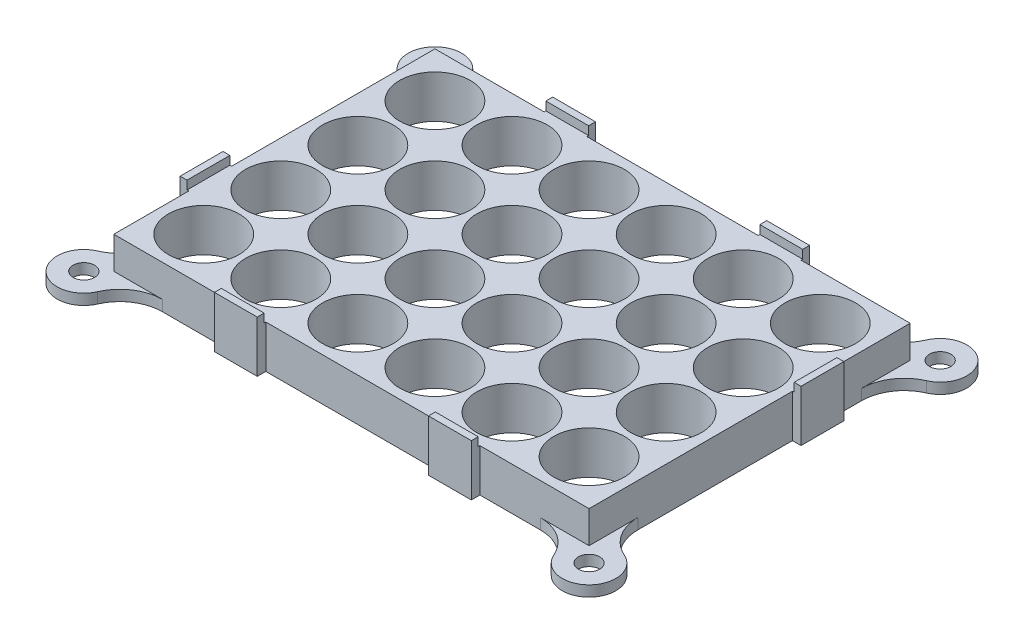
SolidWorks part; units mm, degrees
ref_plane "Front Plane" through (0, 0, 0) normal (0, 0, 1) x (1, 0, 0)
ref_plane "Top Plane" through (0, 0, 0) normal (0, 1, 0) x (1, 0, 0)
ref_plane "Right Plane" through (0, 0, 0) normal (1, 0, 0) x (0, 0, -1)
sketch "Sketch3" plane through (0, 0, 0) normal (0, 1, 0) x (1, 0, 0)
  line L0 (19, 70) -> (37, 70) construction
  line L1 (8.5, 5.5) -> (119.5, 5.5)
  line L2 (8.5, 5.5) -> (8.5, 80.5)
  line L3 (8.5, 80.5) -> (119.5, 80.5)
  line L4 (119.5, 5.5) -> (119.5, 80.5)
  line L5 (19, 70) -> (19, 52) construction
  line L6 (19, 70) -> (109, 70) construction
  line L7 (109, 70) -> (109, 16) construction
  line L8 (109, 16) -> (19, 16) construction
  line L9 (19, 16) -> (19, 70) construction
  circle A0 centre (19, 70) radius 8.25
  circle A1 centre (37, 70) radius 8.25
  circle A2 centre (55, 70) radius 8.25
  circle A3 centre (73, 70) radius 8.25
  circle A4 centre (91, 70) radius 8.25
  circle A5 centre (109, 70) radius 8.25
  circle A6 centre (37, 52) radius 8.25
  circle A7 centre (55, 52) radius 8.25
  circle A8 centre (73, 52) radius 8.25
  circle A9 centre (91, 52) radius 8.25
  circle A10 centre (109, 52) radius 8.25
  circle A11 centre (37, 34) radius 8.25
  circle A12 centre (55, 34) radius 8.25
  circle A13 centre (73, 34) radius 8.25
  circle A14 centre (91, 34) radius 8.25
  circle A15 centre (109, 34) radius 8.25
  circle A16 centre (37, 16) radius 8.25
  circle A17 centre (55, 16) radius 8.25
  circle A18 centre (73, 16) radius 8.25
  circle A19 centre (91, 16) radius 8.25
  circle A20 centre (109, 16) radius 8.25
  circle A21 centre (19, 52) radius 8.25
  circle A22 centre (19, 34) radius 8.25
  circle A23 centre (19, 16) radius 8.25
  dimension "D3" = 16.5
  dimension "D6" = 10.5
  dimension "D1" = 111
  dimension "D2" = 75
  dimension "D7" = 10.5
  dimension "D8" = 5.5
  dimension "D9" = 8.5
  dimension "D10" = 18
  dimension "D11" = 18
  dimension "D4" = 6
  dimension "D5" = 4
extrude "Well light guide" add sketch "Sketch3" along normal blind 10
sketch "Sketch1" plane through (0, 0, 0) normal (0, 1, 0) x (1, 0, 0)
  line L0 (8.5, 5.5) -> (119.5, 5.5) construction
  line L1 (5, 2) -> (123, 2) construction
  line L2 (5, 2) -> (5, 84) construction
  line L3 (5, 84) -> (123, 84) construction
  line L4 (123, 2) -> (123, 84) construction
  line L9 (8.5, 80.5) -> (8.5, 5.5) construction
  line L10 (64, 84) -> (64, 2) construction
  line L11 (5, 43) -> (123, 43) construction
  line L12 (119.5, 80.5) -> (8.5, 80.5) construction
  line L13 (119.5, 5.5) -> (119.5, 80.5) construction
  line L14 (8.5, 5.5) -> (119.5, 5.5) construction
  line L15 (8.5, 80.5) -> (8.5, 5.5) construction
  line L16 (119.5, 80.5) -> (8.5, 80.5) construction
  line L17 (119.5, 5.5) -> (119.5, 80.5) construction
  line L18 (116.75, 84) -> (116.75, 80.5)
  line L19 (123, 77.75) -> (119.5, 77.75)
  line L20 (119.5, 77.75) -> (119.5, 80.5)
  line L21 (119.5, 80.5) -> (116.75, 80.5)
  line L22 (11.25, 84) -> (11.25, 80.5)
  line L23 (8.5, 80.5) -> (11.25, 80.5)
  line L24 (8.5, 77.75) -> (8.5, 80.5)
  line L25 (5, 77.75) -> (8.5, 77.75)
  line L26 (11.25, 2) -> (11.25, 5.5)
  line L27 (8.5, 5.5) -> (11.25, 5.5)
  line L28 (8.5, 8.25) -> (8.5, 5.5)
  line L29 (5, 8.25) -> (8.5, 8.25)
  line L30 (119.5, 5.5) -> (116.75, 5.5)
  line L31 (119.5, 8.25) -> (119.5, 5.5)
  line L32 (123, 8.25) -> (119.5, 8.25)
  line L33 (116.75, 2) -> (116.75, 5.5)
  arc A0 (123, 77.75) -> (116.75, 84) centre (123, 84) ccw
  arc A1 (5, 77.75) -> (11.25, 84) centre (5, 84) cw
  arc A2 (5, 8.25) -> (11.25, 2) centre (5, 2) ccw
  arc A3 (123, 8.25) -> (116.75, 2) centre (123, 2) cw
  circle A4 centre (123, 84) radius 2.5
  circle A5 centre (5, 84) radius 2.5
  circle A6 centre (5, 2) radius 2.5
  circle A7 centre (123, 2) radius 2.5
  point P9 (64, 5.5)
  point P10 (119.5, 43)
  dimension "D3" = 6.25
  dimension "D4" = 5
  dimension "D1" = 118
  dimension "D2" = 82
extrude "PCB mount plate" add sketch "Sketch1" along normal blind 2.5
sketch "Sketch4" plane through (0, 0, 0) normal (0, -1, 0) x (1, 0, 0)
  line L0 (5, -43) -> (123, -43) construction
  line L1 (44, -80.5) -> (34, -80.5)
  line L2 (44, -80.5) -> (44, -82.5)
  line L3 (44, -82.5) -> (34, -82.5)
  line L4 (34, -80.5) -> (34, -82.5)
  line L5 (64, -84) -> (64, -2) construction
  line L6 (5, -43) -> (123, -43) construction
  line L7 (64, -84) -> (64, -2) construction
  line L8 (119.5, -80.5) -> (8.5, -80.5) construction
  line L9 (84, -5.5) -> (84, -3.5)
  line L10 (94, -5.5) -> (84, -5.5)
  line L11 (94, -5.5) -> (94, -3.5)
  line L12 (94, -3.5) -> (84, -3.5)
  line L13 (8.5, -80.5) -> (8.5, -5.5) construction
  line L14 (8.5, -33) -> (6.5, -33)
  line L15 (8.5, -33) -> (8.5, -23)
  line L16 (8.5, -23) -> (6.5, -23)
  line L17 (6.5, -33) -> (6.5, -23)
  line L18 (119.5, -63) -> (121.5, -63)
  line L19 (119.5, -63) -> (119.5, -53)
  line L20 (119.5, -53) -> (121.5, -53)
  line L21 (121.5, -63) -> (121.5, -53)
  line L22 (119.5, -5.5) -> (119.5, -80.5) construction
  line L23 (8.5, -5.5) -> (119.5, -5.5) construction
  line L24 (34, -5.5) -> (44, -5.5)
  line L25 (34, -5.5) -> (34, -3.5)
  line L26 (34, -3.5) -> (44, -3.5)
  line L27 (44, -5.5) -> (44, -3.5)
  line L28 (84, -82.5) -> (94, -82.5)
  line L29 (94, -80.5) -> (94, -82.5)
  line L30 (84, -80.5) -> (94, -80.5)
  line L31 (84, -80.5) -> (84, -82.5)
  dimension "D1" = 2
  dimension "D2" = 10
  dimension "D3" = 2
  dimension "D4" = 10
  dimension "D5" = 10
  dimension "D6" = 10
  dimension "D7" = 2
  dimension "D8" = 10
  dimension "D9" = 20
  dimension "D10" = 10
  dimension "D11" = 2
  dimension "D12" = 20
extrude "Top guide tabs" add sketch "Sketch4" against normal blind 12
sketch "Sketch5" plane through (0, 10, 0) normal (0, 1, 0) x (1, 0, 0)
  line L0 (64, 84) -> (64, 2) construction
  line L1 (84, 5.5) -> (94, 5.5) construction
  line L2 (84, 5.5) -> (94, 5.5) construction
  line L7 (84, 80.5) -> (84, 80.9)
  line L8 (84, 5.5) -> (94, 5.5)
  line L9 (5, 43) -> (123, 43) construction
  line L10 (64, 84) -> (64, 2) construction
  line L11 (5, 43) -> (123, 43) construction
  line L12 (84, 5.5) -> (84, 5.1)
  line L14 (84, 5.1) -> (94, 5.1)
  line L15 (94, 5.5) -> (94, 5.1)
  line L16 (94, 80.5) -> (94, 80.9)
  line L21 (84, 80.9) -> (94, 80.9)
  line L22 (84, 80.5) -> (94, 80.5)
  line L23 (119.5, 53) -> (119.5, 63) construction
  line L24 (119.5, 63) -> (119.9, 63)
  line L25 (119.5, 63) -> (119.5, 53)
  line L26 (119.5, 53) -> (119.9, 53)
  line L27 (119.9, 63) -> (119.9, 53)
  line L28 (119.5, 53) -> (119.5, 63) construction
  line L33 (34, 80.5) -> (34, 80.9)
  line L34 (44, 80.5) -> (34, 80.5)
  line L35 (44, 80.5) -> (44, 80.9)
  line L36 (44, 80.9) -> (34, 80.9)
  line L37 (34, 5.5) -> (34, 5.1)
  line L38 (44, 5.5) -> (34, 5.5)
  line L39 (44, 5.1) -> (34, 5.1)
  line L40 (44, 5.5) -> (44, 5.1)
  line L41 (8.5, 33) -> (8.5, 23)
  line L46 (8.5, 23) -> (8.1, 23)
  line L47 (8.1, 23) -> (8.1, 33)
  line L48 (8.1, 33) -> (8.5, 33)
  point P6 (89, 5.5)
  point P19 (119.5, 58)
  dimension "D1" = 0.4
  dimension "D2" = 0.4
  dimension "D3" = 0.4
extrude "3Dprint spacer" cut sketch "Sketch5" along normal through all
fillet "Fillet1" radius 10 8 edges at (116.75, 1.25, -80.5) (119.5, 1.25, -77.75) (119.5, 1.25, -8.25) (116.75, 1.25, -5.5) (11.25, 1.25, -5.5) (8.5, 1.25, -8.25) (11.25, 1.25, -80.5) (8.5, 1.25, -77.75)
